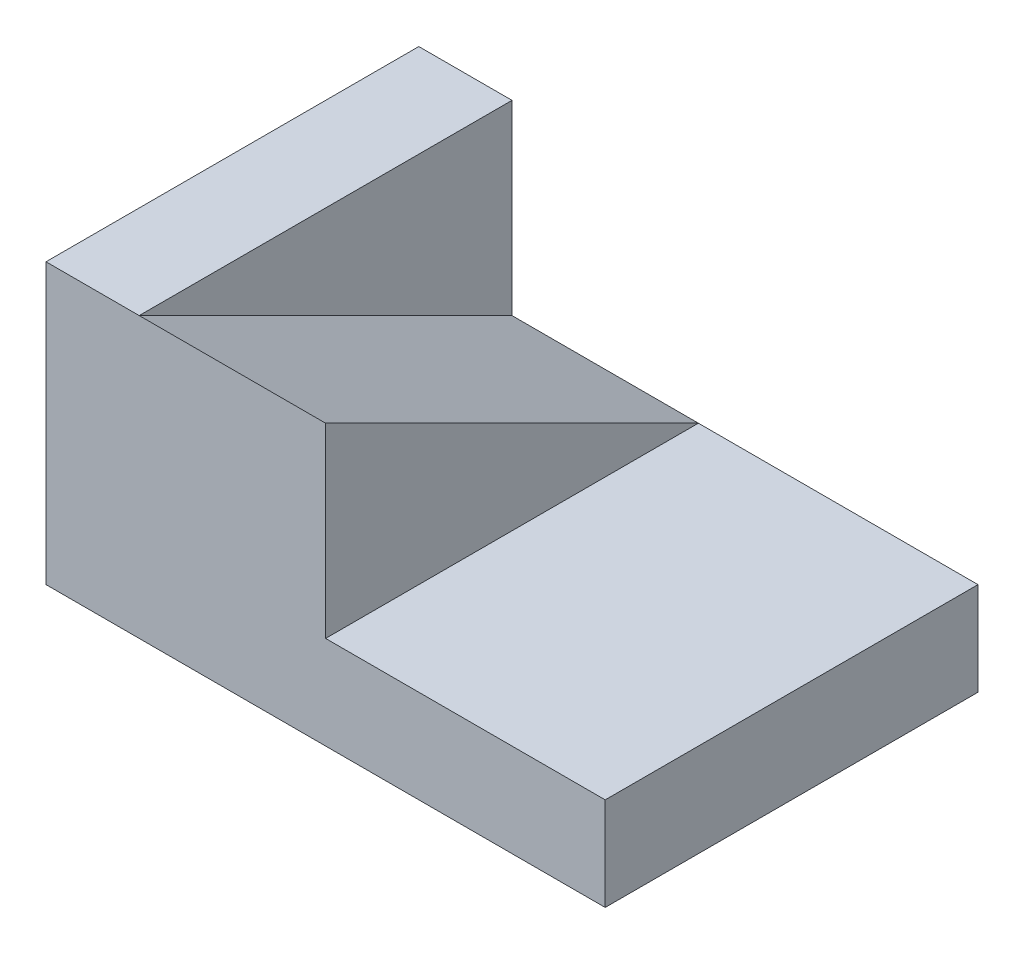
SolidWorks part; units mm, degrees
ref_plane "Front Plane" through (0, 0, 0) normal (0, 0, 1) x (1, 0, 0)
ref_plane "Top Plane" through (0, 0, 0) normal (0, 1, 0) x (1, 0, 0)
ref_plane "Right Plane" through (0, 0, 0) normal (1, 0, 0) x (0, 0, -1)
sketch "Sketch1" plane through (0, 0, 0) normal (1, 0, 0) x (0, 0, -1)
  line L0 (0, 0) -> (40, 0)
  line L1 (40, 0) -> (40, 30)
  line L2 (40, 30) -> (0, 30)
  line L3 (0, 30) -> (0, 0)
  line L4 (0, 10) -> (40, 10)
  line L5 (0, 30) -> (40, 10)
  dimension "D1" = 10
  dimension "D2" = 40
  dimension "D3" = 30
extrude "Boss-Extrude2" add sketch "Sketch1" along normal blind 10 contours L5 L3 L4 | L2 L5 L1 | L4 L3 L0 L1 region at (0, 5, -20) region at (0, 16.6667, -13.3333) region at (0, 23.3333, -26.6667)
extrude "Boss-Extrude3" add sketch "Sketch1<4>" along normal blind 60 contours L4 L3 L0 L1 region at (0, 5, -20)
sketch "Sketch1<4>" plane through (0, 0, 0) normal (1, 0, 0) x (0, 0, -1) same geometry as "Sketch1"
extrude "Boss-Extrude4" add sketch "Sketch1<6>" along normal blind 30 contours L5 L3 L4 region at (0, 16.6667, -13.3333)
sketch "Sketch1<6>" plane through (0, 0, 0) normal (1, 0, 0) x (0, 0, -1) same geometry as "Sketch1"
